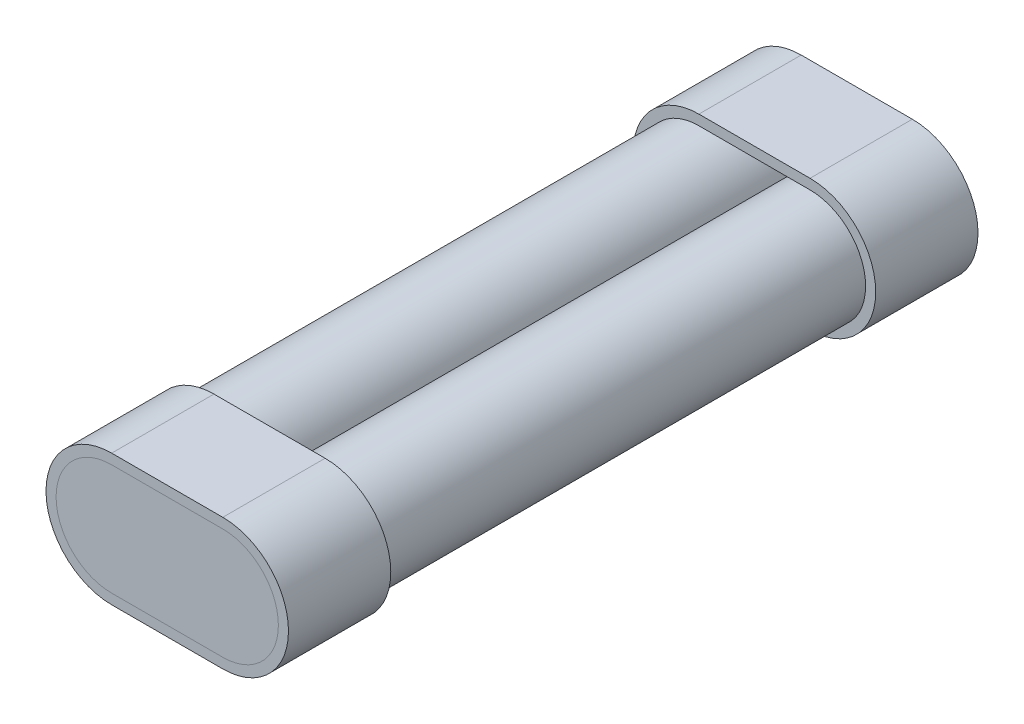
SolidWorks part; units mm, degrees
ref_plane "Plan de face" through (0, 0, 0) normal (0, 0, 1) x (1, 0, 0)
ref_plane "Plan de dessus" through (0, 0, 0) normal (0, 1, 0) x (1, 0, 0)
ref_plane "Plan de droite" through (0, 0, 0) normal (1, 0, 0) x (0, 0, -1)
sketch "Esquisse1" plane through (0, 0, 0) normal (0, 0, 1) x (1, 0, 0)
  line L0 (-11, -11) -> (11, -11)
  line L1 (-11, 0) -> (11, 0) construction
  line L2 (-11, 13) -> (11, 13)
  line L3 (-11, -13) -> (11, -13)
  line L4 (-11, 11) -> (11, 11)
  circle A0 centre (-11, 0) radius 11
  circle A1 centre (11, 0) radius 11
  arc A2 (-11, 13) -> (-11, -13) centre (-11, 0) ccw
  arc A3 (11, -13) -> (11, 13) centre (11, 0) ccw
  point P2 (0, 0)
  point P14 (-24, 0)
  point P15 (24, 0)
  dimension "D1" = 22
  dimension "D3" = 2
  dimension "D5" = 48
extrude "Boss.-Extru.2" add sketch "Esquisse1" against normal blind 132.5 contours A0 | A1 region at (-11, 0, 0) region at (11, 0, 0)
extrude "Boss.-Extru.8" add sketch "Esquisse1<5>" against normal blind 18.25 and the other way blind 2 separate body contours L3 A3 L2 A2 A1 L0 A0 L4 region at (0, 12.4541, 0)
sketch "Esquisse1<5>" plane through (0, 0, 0) normal (0, 0, 1) x (1, 0, 0) same geometry as "Esquisse1"
extrude "Boss.-Extru.29" add sketch "Esquisse1<6>" along normal blind 2 separate body contours A0 | A1 | A1 L4 A0 | A1 A0 L0 region at (0, -8.543, 0) region at (-11, 0, 0) region at (11, 0, 0) region at (0, 8.543, 0)
sketch "Esquisse1<6>" plane through (0, 0, 0) normal (0, 0, 1) x (1, 0, 0) same geometry as "Esquisse1"
sketch "Esquisse8" plane through (0, 0, -132.5) normal (0, 0, -1) x (-1, 0, 0)
  line L0 (-11, -11) -> (11, -11)
  line L1 (-11, 0) -> (11, 0) construction
  line L2 (-11, 13) -> (11, 13)
  line L3 (-11, -13) -> (11, -13)
  line L4 (-11, 11) -> (11, 11)
  circle A0 centre (-11, 0) radius 11
  circle A1 centre (11, 0) radius 11
  arc A2 (-11, 13) -> (-11, -13) centre (-11, 0) ccw
  arc A3 (11, -13) -> (11, 13) centre (11, 0) ccw
  point P2 (0, 0)
  point P13 (-24, 0)
  point P18 (24, 0)
  circle M8 centre (11, 0) radius 11
  dimension "D1" = 22
  dimension "D2" = 13
  dimension "D4" = 48
extrude "Boss.-Extru.33" add sketch "Esquisse8" against normal blind 18.25 and the other way blind 2 separate body contours L3 A3 L2 A2 A0 L4 L0 M8 region at (0, 12.4541, -132.5)
extrude "Boss.-Extru.34" add sketch "Esquisse8<3>" along normal blind 2 separate body contours A0 | A0 L4 M8 | M8 | A0 L0 M8 region at (0, -8.543, -132.5) region at (11, 0, -132.5) region at (-11, 0, -132.5) region at (0, 8.543, -132.5)
sketch "Esquisse8<3>" plane through (0, 0, -132.5) normal (0, 0, -1) x (-1, 0, 0) same geometry as "Esquisse8"
